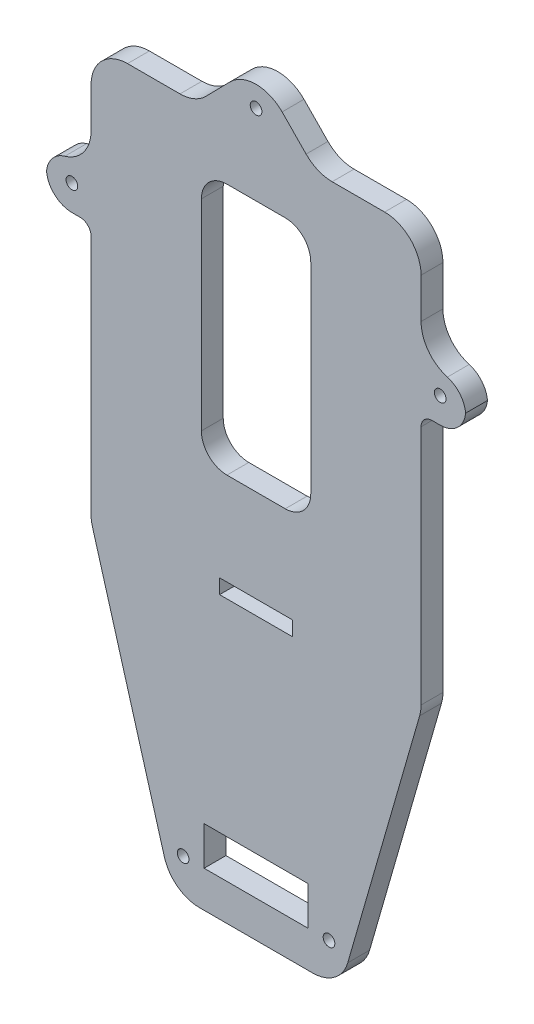
SolidWorks part; units mm, degrees
material "MDF"
ref_plane "Plano frontal" through (0, 0, 0) normal (0, 0, 1) x (1, 0, 0)
ref_plane "Plano superior" through (0, 0, 0) normal (0, 1, 0) x (1, 0, 0)
ref_plane "Plano direito" through (0, 0, 0) normal (1, 0, 0) x (0, 0, -1)
sketch "Esboço1" plane through (0, 0, 0) normal (0, 0, 1) x (1, 0, 0)
  line L1 (-45.25, -56.75) -> (45.25, -56.75) construction
  line L2 (-45.25, -56.75) -> (-45.25, 56.75) construction
  line L3 (-45.25, 56.75) -> (45.25, 56.75) construction
  line L4 (45.25, -56.75) -> (45.25, 13.75) construction
  line L5 (-45.25, -56.75) -> (45.25, 56.75) construction
  line L6 (-45.25, 56.75) -> (45.25, -56.75) construction
  line L18 (-45.25, -56.75) -> (21.552, -56.75) construction
  line L20 (-45.25, -56.75) -> (-23.0595, -133.85)
  line L21 (-23.0595, -133.85) -> (23.0595, -133.85)
  line L23 (14.25, -113.25) -> (-14.25, -113.25)
  line L24 (14.25, -113.25) -> (14.25, -123.85)
  line L25 (14.25, -123.85) -> (-14.25, -123.85)
  line L26 (-14.25, -113.25) -> (-14.25, -123.85)
  line L27 (14.25, -113.25) -> (-14.25, -123.85) construction
  line L28 (14.25, -123.85) -> (-14.25, -113.25) construction
  line L29 (-15.1, -125.35) -> (15.1, -125.35) construction
  line L30 (-15.1, -125.35) -> (-15.1, -111.75) construction
  line L31 (-15.1, -111.75) -> (15.1, -111.75) construction
  line L32 (15.1, -125.35) -> (15.1, -111.75) construction
  line L33 (-15.1, -125.35) -> (15.1, -111.75) construction
  line L34 (-15.1, -111.75) -> (15.1, -125.35) construction
  line L39 (-45.25, 25.75) -> (-45.25, 56.75)
  line L48 (15, -27.35) -> (-15, -27.35)
  line L50 (-45.25, 25.75) -> (-57.5, 25.75)
  line L52 (0, 0) -> (0, 36.35) construction
  line L54 (45.25, 25.75) -> (57.5, 25.75)
  line L55 (45.25, 25.75) -> (45.25, 56.75)
  line L56 (45.25, 25.75) -> (45.25, 56.75) construction
  line L57 (-45.25, 56.75) -> (-16.6633, 56.75)
  line L58 (-16.6633, 56.75) -> (0, 73.75)
  line L59 (0, 73.75) -> (16.6633, 56.75)
  line L60 (16.6633, 56.75) -> (45.25, 56.75)
  line L61 (-57.5, 25.75) -> (-57.5, 13.75)
  line L62 (-57.5, 13.75) -> (-45.25, 13.75)
  line L63 (57.5, 13.75) -> (45.25, 13.75)
  line L64 (57.5, 25.75) -> (57.5, 13.75)
  line L65 (23.0595, -133.85) -> (45.25, -56.75)
  line L66 (45.25, 13.75) -> (45.25, -56.75)
  line L67 (-45.25, -56.75) -> (-45.25, 13.75)
  line L68 (15, -27.35) -> (15, 41.75)
  line L69 (10, -52.75) -> (-10, -52.75)
  line L70 (10, -52.75) -> (10, -56.75)
  line L71 (10, -56.75) -> (-10, -56.75)
  line L72 (-10, -52.75) -> (-10, -56.75)
  line L73 (10, -52.75) -> (-10, -56.75) construction
  line L74 (10, -56.75) -> (-10, -52.75) construction
  line L75 (15, 41.75) -> (-15, 41.75)
  line L76 (-15, -27.35) -> (-15, 41.75)
  line L77 (15, -27.35) -> (-15, 41.75) construction
  line L78 (15, 41.75) -> (-15, -27.35) construction
  circle A0 centre (0, 63.75) radius 1.6
  circle A1 centre (-50.5, -80.53) radius 1.6
  circle A2 centre (-50.5, 20.75) radius 1.6
  circle A3 centre (50.5, 20.75) radius 1.6
  point P0 (0, 0)
  point P6 (0, -54.75)
  point P16 (0, -133.85)
  point P27 (0, -118.55)
  point P32 (0, -118.55)
  point P39 (0, 0)
  point P42 (0, 7.2)
  dimension "D3" = 3.2
  dimension "D10" = 10
  dimension "D4" = 7
  dimension "D5" = 10
  dimension "D9" = 43
  dimension "D19" = 101
  dimension "D1" = 90.5
  dimension "D2" = 113.5
  dimension "D6" = 5
  dimension "D7" = 55
  dimension "D8" = 10
  dimension "D11" = 28.5
  dimension "D12" = 10.6
  dimension "D13" = 13.6
  dimension "D14" = 30.2
  dimension "D15" = 7
  dimension "D16" = 144.28
  dimension "D17" = 25.4
  dimension "D18" = 7
  dimension "D20" = 15
  dimension "D21" = 20
  dimension "D22" = 7
  dimension "D23" = 4
  dimension "D24" = 30
extrude "Ressalto-extrusão1" add sketch "Esboço1" along normal blind 6 contours L23 L24 L25 | L26 L23 L25 A2 A1 A0 region at (0, -31.6811, 0)
fillet "Filete3" radius 3 2 edges at (45.25, 13.75, 3) (-45.25, 13.75, 3)
fillet "Filete4" radius 10 11 edges at (-16.6633, 56.75, 3) (16.6633, 56.75, 3) (-45.25, 25.75, 3) (45.25, 25.75, 3) (0, 73.75, 3) (45.25, 56.75, 3) (-45.25, 56.75, 3) (-45.25, -56.75, 3) (45.25, -56.75, 3) (23.0595, -133.85, 3) (-23.0595, -133.85, 3)
fillet "Filete5" radius 7 8 edges at (57.5, 13.75, 3) (57.5, 25.75, 3) (-57.5, 13.75, 3) (-57.5, 25.75, 3) (-15, -27.35, 3) (15, -27.35, 3) (15, 41.75, 3) (-15, 41.75, 3)
sketch "Esboço2" plane through (0, 0, 6) normal (0, 0, 1) x (1, 0, 0)
  line L0 (-20, -123.85) -> (20, -123.85) construction
  line L1 (-15.5317, -133.85) -> (15.5317, -133.85) construction
  circle A0 centre (-20, -123.85) radius 1.6
  circle A1 centre (20, -123.85) radius 1.6
  point P4 (0, -123.85)
  point P5 (0, -133.85)
  point P6 (0, 0)
  dimension "D2" = 3.2
  dimension "D1" = 40
  dimension "D3" = 10
extrude "Corte-extrusão1" cut sketch "Esboço2" against normal blind 10
equation "\"mm\"=5"
